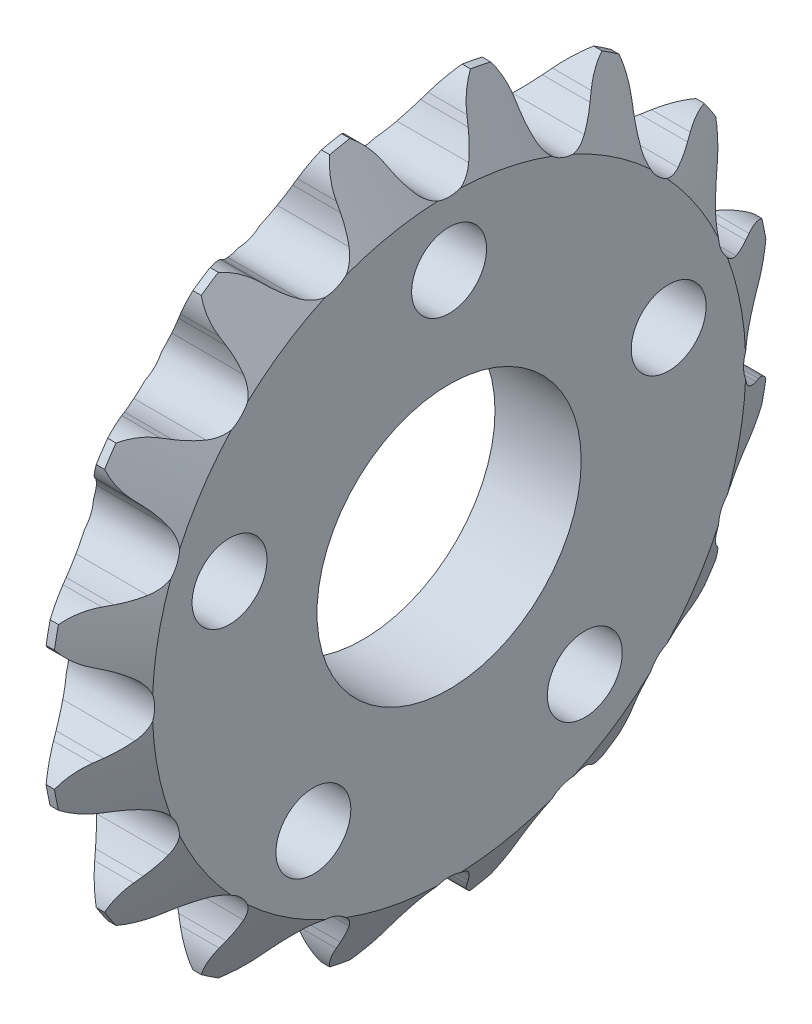
SolidWorks part; units mm, degrees
material "Alloy Steel"
ref_plane "Front Plane" through (0, 0, 0) normal (0, 0, 1) x (1, 0, 0)
ref_plane "Top Plane" through (0, 0, 0) normal (0, 1, 0) x (1, 0, 0)
ref_plane "Right Plane" through (0, 0, 0) normal (1, 0, 0) x (0, 0, -1)
ref_axis "X AXIS" through (-88.99, 0, 0) along (1, 0, 0)
ref_axis "Y AXIS" through (0, -55, 0) along (0, 1, 0)
ref_axis "Z AXIS" through (0, 0, 55) along (0, 0, -1)
other "Freeze***"
sketch "Sketch1" plane through (0, 0, 0) normal (1, 0, 0) x (0, 0, -1)
  line L0 (0, 16.2745) -> (-6.228, 15.0357) construction
  line L1 (-1.896, 16.1459) -> (-2.0514, 16.491)
  line L2 (-1.896, 16.1459) -> (2.0601, 17.928) construction
  line L3 (2.0601, 17.928) -> (0, 16.2745) construction
  line L4 (0, 16.2745) -> (-1.9539, 16.2745) construction
  line L5 (-3.5639, 17.9168) -> (-3.114, 15.6551) construction
  line L6 (0, 16.2745) -> (0, 14.5772) construction
  circle A0 centre (0, 0) radius 16.2745 construction
  arc A1 (-1.3237, 15.2121) -> (0, 14.5772) centre (0, 16.2745) ccw
  arc A2 (-1.3237, 15.2121) -> (-1.896, 16.1459) centre (2.0601, 17.928) cw
  arc A3 (-2.0514, 16.491) -> (-3.5639, 17.9168) centre (-4.534, 15.3726) ccw
sketch "Sketch2" plane through (0, 0, 0) normal (0, 0, 1) x (1, 0, 0)
  line L0 (0, 0) -> (0, 17.862) construction
  line L1 (-0.2064, 17.862) -> (0.2064, 17.862)
  line L2 (0.2064, 17.862) -> (2.1336, 14.687)
  line L3 (2.1336, 14.687) -> (2.1336, 0)
  line L4 (-2.1336, 0) -> (2.1336, 0)
  line L5 (-2.1336, 14.687) -> (-2.1336, 0)
  line L6 (-0.2064, 17.862) -> (-2.1336, 14.687)
  dimension "D1" = 17.862
  dimension "D2" = 4.2672
revolve "Revolve1" add sketch "Sketch2" angle 360 about L4
sketch "Sketch3" plane through (0, 0, 0) normal (1, 0, 0) x (0, 0, -1)
  line L0 (-1.896, 16.1459) -> (-2.0514, 16.491) construction
  line L1 (-1.896, 16.1459) -> (-2.0514, 16.491)
  line L2 (0, 14.5772) -> (0, 0) construction
  line L3 (1.896, 16.1459) -> (2.0514, 16.491)
  arc A0 (-2.0514, 16.491) -> (-3.5639, 17.9168) centre (-4.534, 15.3726) ccw construction
  arc A1 (-1.896, 16.1459) -> (-1.3237, 15.2121) centre (2.0601, 17.928) ccw construction
  arc A2 (-1.3237, 15.2121) -> (0, 14.5772) centre (0, 16.2745) ccw construction
  arc A3 (-2.0514, 16.491) -> (-3.5639, 17.9168) centre (-4.534, 15.3726) ccw
  arc A4 (-1.896, 16.1459) -> (-1.3237, 15.2121) centre (2.0601, 17.928) ccw
  arc A5 (-1.3237, 15.2121) -> (1.3237, 15.2121) centre (0, 16.2745) ccw
  arc A6 (1.896, 16.1459) -> (1.3237, 15.2121) centre (-2.0601, 17.928) cw
  arc A7 (2.0514, 16.491) -> (3.5639, 17.9168) centre (4.534, 15.3726) cw
  arc A8 (-3.5639, 17.9168) -> (3.5639, 17.9168) centre (0, 0) cw
extrude "Cut-Extrude1" cut sketch "Sketch3" against normal through all both and the other way through all contours A8 A3 L1 A4 A5 A6 L3 A7 region at (0, 16.7606, 0)
pattern_circular "CirPattern1" count 16 over 360 about axis through (-88.99, 0, 0) along (1, 0, 0) of "Cut-Extrude1"
sketch "Sketch4" plane through (2.1336, 0, 0) normal (1, 0, 0) x (0, 0, -1)
  line L0 (0, 0) -> (0, 11.43) construction
  circle A0 centre (0, 0) radius 6.5405
  circle A1 centre (0, 11.43) radius 1.8542
  circle A2 centre (10.8706, 3.5321) radius 1.8542
  circle A3 centre (6.7184, -9.2471) radius 1.8542
  circle A4 centre (-6.7184, -9.2471) radius 1.8542
  circle A5 centre (-10.8706, 3.5321) radius 1.8542
  point P15 (0, 0)
  dimension "D1" = 13.081
  dimension "D2" = 5
  dimension "D3" = 3.7084
  dimension "D4" = 11.43
extrude "Cut-Extrude2" cut sketch "Sketch4" against normal through all
equation "\"p\"= 2 / 8"
equation "\"n\" = 16"
equation "\"Dr\"= 0.13"
equation "\"Ds\"= 1.005 * \"Dr\" + 0.003"
equation "\"PD\"= \"p\" * cosec ( 180 / \"n\" )"
equation "\"A\"= 35 + 60 / \"n\""
equation "\"B\"= 18 - 56 / \"n\""
equation "\"ac\"= 0.8 * \"Dr\""
equation "\"ab\"= 1.4 * \"Dr\""
equation "\"D1@Sketch1\"=\"PD\""
equation "\"D2@Sketch1\"=\"p\""
equation "\"D3@Sketch1\"=\"Ds\""
equation "\"D4@Sketch1\"=\"A\""
equation "\"D5@Sketch1\"=\"B\""
equation "\"D6@Sketch1\"=\"ac\""
equation "\"D7@Sketch1\"=\"ab\""
equation "\"D1@Sketch2\"=(\"PD\"+\"p\"/2)/2"
equation "\"D4@Sketch2\"=\"p\"/2"
equation "\"D1@CirPattern1\"=\"n\""
